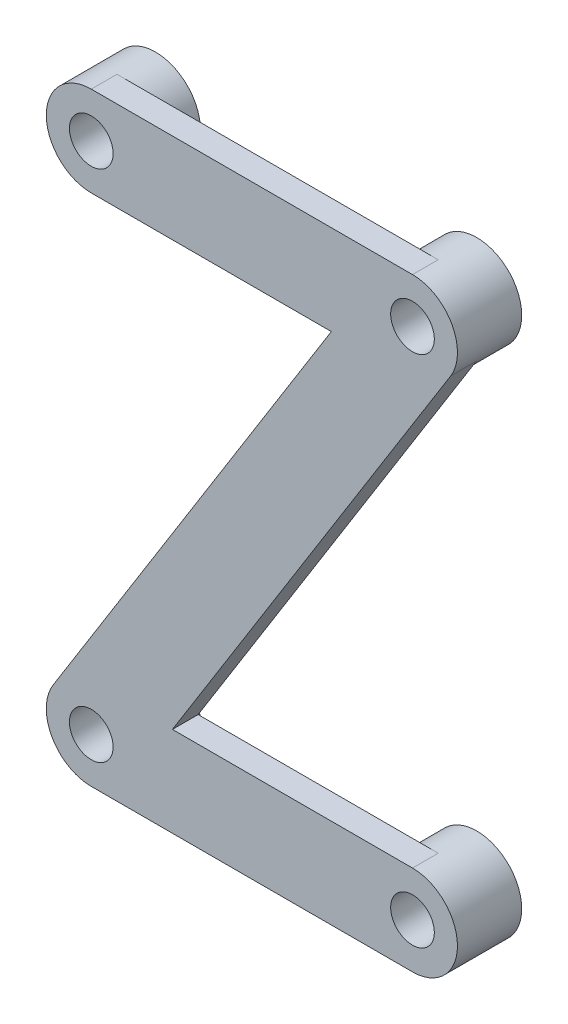
SolidWorks part; units mm, degrees
ref_plane "Спереди" through (0, 0, 0) normal (0, 0, 1) x (1, 0, 0)
ref_plane "Сверху" through (0, 0, 0) normal (0, 1, 0) x (1, 0, 0)
ref_plane "Справа" through (0, 0, 0) normal (1, 0, 0) x (0, 0, -1)
sketch "Эскиз1" plane through (0, 0, 0) normal (0, 0, 1) x (1, 0, 0)
  line L10 (-12.5, 23.5) -> (12.5, 23.5)
  line L11 (-12.5, 20) -> (12.5, 20) construction
  line L12 (-12.5, 20) -> (-12.5, -20) construction
  line L13 (-12.5, -20) -> (12.5, -20) construction
  line L14 (12.5, 20) -> (12.5, -20) construction
  line L15 (-12.5, 20) -> (12.5, -20) construction
  line L16 (-12.5, -20) -> (12.5, 20) construction
  line L17 (-12.5, 16.5) -> (6.1851, 16.5)
  line L18 (-6.1851, -16.5) -> (12.5, -16.5)
  line L19 (15.468, 18.145) -> (-6.1851, -16.5)
  line L21 (-12.5, -23.5) -> (12.5, -23.5)
  line L22 (6.1851, 16.5) -> (-15.468, -18.145)
  circle A8 centre (12.5, 20) radius 3.5
  circle A9 centre (12.5, -20) radius 3.5
  circle A10 centre (-12.5, -20) radius 3.5
  circle A11 centre (-12.5, 20) radius 3.5
  circle A12 centre (-12.5, 20) radius 1.7
  circle A13 centre (12.5, 20) radius 1.7
  circle A14 centre (-12.5, -20) radius 1.7
  circle A15 centre (12.5, -20) radius 1.7
  point P18 (0, 0)
  dimension "D6" = 7
  dimension "D1" = 3.4
  dimension "D4" = 25
  dimension "D5" = 40
extrude "Основа" add sketch "Эскиз1" against normal blind 2 contours A11 L17 L22 A10 L21 A9 L18 L19 A8 L10 region at (0, 0, 0)
extrude "Стойки" add sketch "Эскиз1<3>" against normal blind 5 contours A11 | A8 | A10 | A9 region at (-10.0951, 22.4049, 0) region at (14.9049, 22.4049, 0) region at (-11.5624, -16.7308, 0) region at (14.9049, -17.5951, 0)
sketch "Эскиз1<3>" plane through (0, 0, 0) normal (0, 0, 1) x (1, 0, 0) same geometry as "Эскиз1"
